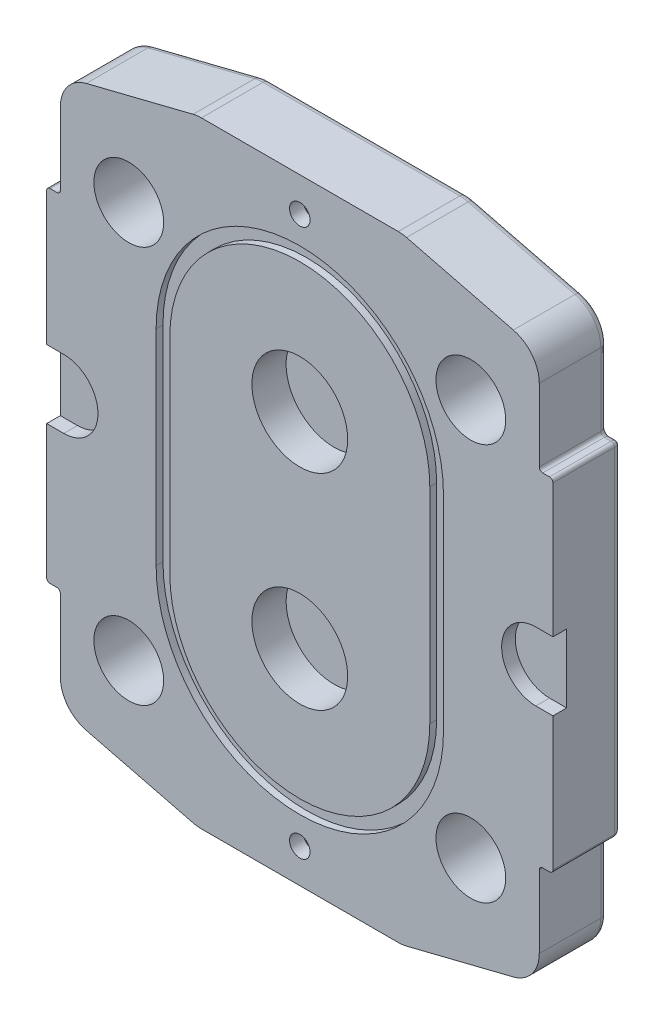
SolidWorks part; units mm, degrees
ref_plane "Front Plane" through (0, 0, 0) normal (0, 0, 1) x (1, 0, 0)
ref_plane "Top Plane" through (0, 0, 0) normal (0, 1, 0) x (1, 0, 0)
ref_plane "Right Plane" through (0, 0, 0) normal (1, 0, 0) x (0, 0, -1)
sketch "Sketch1" plane through (0, 0, 0) normal (0, 0, 1) x (1, 0, 0)
  line L0 (-35, -25) -> (-35, -40)
  line L1 (15, 45) -> (-15, 45)
  line L2 (35, 40) -> (35, 25)
  line L3 (15, -45) -> (-15, -45)
  line L4 (-35, 40) -> (-35, 25)
  line L5 (35, 45) -> (-35, -45) construction
  line L6 (35, -45) -> (-35, 45) construction
  line L7 (-37, -25) -> (-35, -25)
  line L8 (-37, -25) -> (-37, 25)
  line L9 (-37, 25) -> (-35, 25)
  line L11 (-15, 45) -> (-35, 40)
  line L12 (35, 40) -> (15, 45)
  line L13 (35, -25) -> (37, -25)
  line L15 (35, 25) -> (37, 25)
  line L16 (37, -25) -> (37, 25)
  line L17 (-15, -45) -> (-35, -40)
  line L18 (35, -40) -> (15, -45)
  line L19 (35, -25) -> (35, -40)
  point P0 (0, 0)
  point P6 (-37, 0)
  point P10 (-36, 25)
  point P11 (37, 0)
  dimension "D1" = 70
  dimension "D2" = 90
  dimension "D3" = 50
  dimension "D4" = 37
  dimension "D6" = 50
  dimension "D7" = 20
  dimension "D9" = 37
  dimension "D10" = 20
  dimension "D11" = 20
  dimension "D12" = 5
  dimension "D13" = 20
  dimension "D14" = 5
  dimension "D15" = 20
  dimension "D16" = 5
  dimension "D17" = 5
  dimension "D18" = 20
  dimension "D19" = 37
  dimension "D20" = 74
extrude "Boss-Extrude1" add sketch "Sketch1" against normal blind 10
fillet "Fillet1" radius 5 8 edges at (-35, -40, -5) (-15, -45, -5) (15, -45, -5) (35, -40, -5) (15, 45, -5) (-15, 45, -5) (-35, 40, -5) (35, 40, -5)
fillet "Fillet2" radius 0.5 8 edges at (35, -25, -5) (37, -25, -5) (35, 25, -5) (-35, 25, -5) (-37, 25, -5) (-37, -25, -5) (-35, -25, -5) (37, 25, -5)
sketch "Sketch2" plane through (0, 0, 0) normal (0, 0, 1) x (1, 0, 0)
  line L0 (34.5, 0) -> (39.5, 0) construction
  line L1 (37, -24.5) -> (37, 24.5) construction
  line L2 (34.5, 5) -> (39.5, 5)
  line L3 (34.5, -5) -> (39.5, -5)
  line L4 (0, -15) -> (0, 15) construction
  line L5 (-20, -15) -> (-20, 15)
  line L6 (20, -15) -> (20, 15)
  line L7 (0, 0) -> (0, 52.7891) construction
  line L8 (0, 0) -> (72.4136, 0) construction
  line L9 (-34.5, 0) -> (-39.5, 0) construction
  line L10 (-34.5, 5) -> (-39.5, 5)
  line L11 (-34.5, -5) -> (-39.5, -5)
  circle A0 centre (0, 40) radius 1.5
  arc A1 (34.5, 5) -> (34.5, -5) centre (34.5, 0) ccw
  arc A2 (39.5, -5) -> (39.5, 5) centre (39.5, 0) ccw
  arc A3 (-20, -15) -> (20, -15) centre (0, -15) ccw
  arc A4 (20, 15) -> (-20, 15) centre (0, 15) ccw
  circle A5 centre (0, 15) radius 7
  circle A6 centre (0, -40) radius 1.5
  circle A7 centre (0, -15) radius 7
  arc A8 (-34.5, 5) -> (-34.5, -5) centre (-34.5, 0) cw
  arc A9 (-39.5, -5) -> (-39.5, 5) centre (-39.5, 0) cw
  point P7 (37, 0)
  point P14 (0, 0)
  point P30 (-37, 0)
  dimension "D1" = 3
  dimension "D4" = 5
  dimension "D7" = 14
  dimension "D2" = 40
  dimension "D3" = 5
  dimension "D5" = 40
  dimension "D6" = 30
extrude "Cut-Extrude-Thin1" cut sketch "Sketch2" against normal blind 1 thin contours A4 L5 A3 L6 thin type mid plane wall 2
extrude "Cut-Extrude1" cut sketch "Sketch2<3>" against normal blind 2 contours A0 | A6 | A9 L10 A8 L11 | A2 L2 A1 L3
sketch "Sketch2<3>" plane through (0, 0, 0) normal (0, 0, 1) x (1, 0, 0) same geometry as "Sketch2"
extrude "Cut-Extrude2" cut sketch "Sketch2<4>" against normal blind 5 contours A5 | A7
sketch "Sketch2<4>" plane through (0, 0, 0) normal (0, 0, 1) x (1, 0, 0) same geometry as "Sketch2"
extrude "Boss-Extrude2" add sketch "Sketch2<5>" against normal blind 2 draft 5 from surface contours A4 L5 A3 L6 starting at face at (0, 0, -10)
sketch "Sketch2<5>" plane through (0, 0, 0) normal (0, 0, 1) x (1, 0, 0) same geometry as "Sketch2"
fillet "Fillet3" radius 1 40 edges at (0, 35, -10) (20, 0, -10) (0, -35, -10) (-20, 0, -10) (36.8536, 24.8536, -10) (36, 25, -10) (35.1464, 25.1464, -10) (35, 30.7981, -10) (33.941, 39.1732, -10) (23.4049, 42.8988, -10) (14.9954, 44.9625, -10) (0, 45, -10) (-14.9954, 44.9625, -10) (-23.4049, 42.8988, -10) (-33.941, 39.1732, -10) (-35, 30.7981, -10) (-35.1464, 25.1464, -10) (-36, 25, -10) (-36.8536, 24.8536, -10) (-37, 0, -10) (-36.8536, -24.8536, -10) (-36, -25, -10) (-35.1464, -25.1464, -10) (-35, -30.7981, -10) (-33.941, -39.1732, -10) (-23.4049, -42.8988, -10) (-14.9954, -44.9625, -10) (0, -45, -10) (14.9954, -44.9625, -10) (23.4049, -42.8988, -10) (33.941, -39.1732, -10) (35, -30.7981, -10) (35.1464, -25.1464, -10) (36, -25, -10) (36.8536, -24.8536, -10) (37, 0, -10) (0, -34.825, -12) (19.825, 0, -12) (0, 34.825, -12) (-19.825, 0, -12)
sketch "Sketch5" plane through (0, 0, 0) normal (0, 0, 1) x (1, 0, 0)
  line L0 (-35, 36.0961) -> (-35, 25.5) construction
  line L1 (14.3845, 45) -> (-14.3845, 45) construction
  line L2 (35, 25.5) -> (35, 36.0961) construction
  line L3 (-14.3845, -45) -> (14.3845, -45) construction
  point P0 (-25, 29)
  point P2 (25, 29)
  point P4 (25, -29)
  point P6 (-25, -29)
  dimension "D1" = 10
  dimension "D2" = 16
  dimension "D3" = 10
  dimension "D4" = 16
hole_wizard "Ø10.2 (10.2) Diameter Hole1" positions "Sketch5" profile "Sketch6" hole size "Ø10.2" standard "ISO" end condition up to next
sketch "Sketch6" plane through (-25, 29, 0) normal (1, 0, 0) x (0, -1, 0)
  line L0 (0, 0) -> (0, 10)
  line L1 (0, 10) -> (5.1, 10)
  line L2 (5.1, 10) -> (5.1, 0)
  line L5 (5.1, 0) -> (0, 0)
  line L11 (0, -6.35) -> (0, 107.95) construction
  dimension "Thru Hole Dia." = 10.2
  dimension "Thru Hole Depth" = 10
